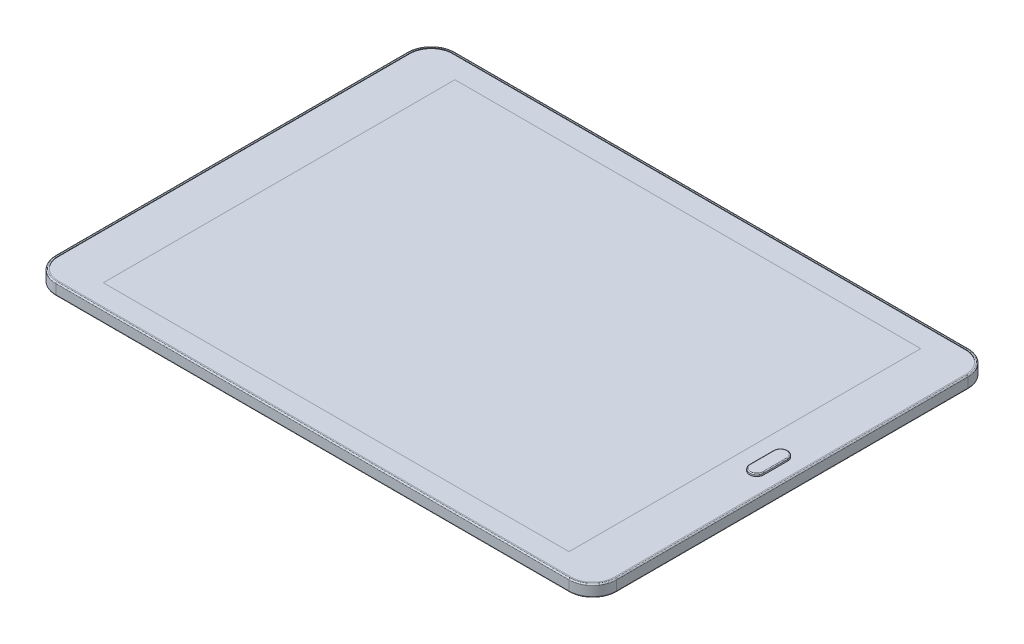
SolidWorks part; units mm, degrees
ref_plane "Front Plane" through (0, 0, 0) normal (0, 0, 1) x (1, 0, 0)
ref_plane "Top Plane" through (0, 0, 0) normal (0, 1, 0) x (1, 0, 0)
ref_plane "Right Plane" through (0, 0, 0) normal (1, 0, 0) x (0, 0, -1)
sketch "Sketch1" plane through (0, 0, 0) normal (0, 1, 0) x (1, 0, 0)
  line L1 (108, 84) -> (-108, 84)
  line L2 (118, 74) -> (118, -74)
  line L3 (108, -84) -> (-108, -84)
  line L4 (-118, 74) -> (-118, -74)
  line L5 (118, 84) -> (-118, -84) construction
  line L6 (118, -84) -> (-118, 84) construction
  arc A0 (-108, -84) -> (-118, -74) centre (-108, -74) cw
  arc A1 (118, -74) -> (108, -84) centre (108, -74) cw
  arc A2 (108, 84) -> (118, 74) centre (108, 74) cw
  arc A3 (-108, 84) -> (-118, 74) centre (-108, 74) ccw
  point P0 (0, 0)
  dimension "D3" = 10
  dimension "D1" = 236
  dimension "D2" = 168
extrude "Boss-Extrude1" add sketch "Sketch1" along normal blind 5
sketch "Sketch2" plane through (0, 5, 0) normal (0, 1, 0) x (1, 0, 0)
  line L8 (-108, -83) -> (108, -83)
  line L9 (117, -74) -> (117, 74)
  line L10 (108, 83) -> (-108, 83)
  line L11 (-117, 74) -> (-117, -74)
  line L12 (-108, -83) -> (108, -83)
  line L13 (117, -74) -> (117, 74)
  line L14 (108, 83) -> (-108, 83)
  line L15 (-117, 74) -> (-117, -74)
  arc A8 (-117, -74) -> (-108, -83) centre (-108, -74) ccw
  arc A9 (108, -83) -> (117, -74) centre (108, -74) ccw
  arc A10 (117, 74) -> (108, 83) centre (108, 74) ccw
  arc A11 (-108, 83) -> (-117, 74) centre (-108, 74) ccw
  arc A12 (-117, -74) -> (-108, -83) centre (-108, -74) ccw
  arc A13 (108, -83) -> (117, -74) centre (108, -74) ccw
  arc A14 (117, 74) -> (108, 83) centre (108, 74) ccw
  arc A15 (-108, 83) -> (-117, 74) centre (-108, 74) ccw
  dimension "D1" = 1
extrude "Cut-Extrude1" cut sketch "Sketch2" against normal blind 0.2
sketch "Sketch3" plane through (0, 4.8, 0) normal (0, 1, 0) x (1, 0, 0)
  line L0 (108, 84) -> (-108, 84) construction
  line L1 (-98, 74) -> (98, 74)
  line L2 (-98, 74) -> (-98, -74)
  line L3 (-98, -74) -> (98, -74)
  line L4 (98, 74) -> (98, -74)
  line L6 (-108, -84) -> (108, -84) construction
  line L7 (118, -74) -> (118, 74) construction
  line L8 (-118, 74) -> (-118, -74) construction
  dimension "D1" = 10
  dimension "D2" = 10
  dimension "D3" = 20
  dimension "D4" = 20
split line "Split Line1"
sketch "Sketch6" plane through (0, 4.8, 0) normal (0, 1, 0) x (1, 0, 0)
  line L0 (0, 0) -> (108, 0) construction
  line L1 (108, 5) -> (108, -5) construction
  line L2 (111, 5) -> (111, -5)
  line L3 (105, 5) -> (105, -5)
  line L4 (118, -74) -> (118, 74) construction
  arc A0 (111, 5) -> (105, 5) centre (108, 5) ccw
  arc A1 (105, -5) -> (111, -5) centre (108, -5) ccw
  point P5 (108, 0)
  dimension "D1" = 10
  dimension "D2" = 6
  dimension "D3" = 10
extrude "Boss-Extrude2" add sketch "Sketch6" along normal blind 1
fillet "Fillet1" radius 0.4 4 edges at (105, 5.8, 0) (108, 5.8, -8) (111, 5.8, 0) (108, 5.8, 8)
sketch "Sketch7" plane through (0, 0, 0) normal (0, -1, 0) x (1, 0, 0)
  line L0 (-109, 0) -> (0, 0) construction
  line L1 (-112, 6) -> (-106, 6)
  line L2 (-115, 3) -> (-115, -3)
  line L3 (-112, -6) -> (-106, -6)
  line L4 (-103, 3) -> (-103, -3)
  line L5 (-115, 6) -> (-103, -6) construction
  line L6 (-115, -6) -> (-103, 6) construction
  line L7 (-118, -74) -> (-118, 74) construction
  arc A0 (-115, -3) -> (-112, -6) centre (-112, -3) ccw
  arc A1 (-106, -6) -> (-103, -3) centre (-106, -3) ccw
  arc A2 (-106, 6) -> (-103, 3) centre (-106, 3) cw
  arc A3 (-112, 6) -> (-115, 3) centre (-112, 3) ccw
  point P0 (-109, 0)
  dimension "D4" = 3
  dimension "D1" = 9
  dimension "D2" = 12
  dimension "D3" = 12
extrude "Boss-Extrude3" add sketch "Sketch7" along normal blind 1
sketch "Sketch8" plane through (0, -1, 0) normal (0, -1, 0) x (1, 0, 0)
  line L8 (-112, -5) -> (-106, -5)
  line L9 (-104, -3) -> (-104, 3)
  line L10 (-106, 5) -> (-112, 5)
  line L11 (-114, 3) -> (-114, -3)
  line L12 (-112, -5) -> (-106, -5)
  line L13 (-104, -3) -> (-104, 3)
  line L14 (-106, 5) -> (-112, 5)
  line L15 (-114, 3) -> (-114, -3)
  arc A8 (-114, -3) -> (-112, -5) centre (-112, -3) ccw
  arc A9 (-106, -5) -> (-104, -3) centre (-106, -3) ccw
  arc A10 (-104, 3) -> (-106, 5) centre (-106, 3) ccw
  arc A11 (-112, 5) -> (-114, 3) centre (-112, 3) ccw
  arc A12 (-114, -3) -> (-112, -5) centre (-112, -3) ccw
  arc A13 (-106, -5) -> (-104, -3) centre (-106, -3) ccw
  arc A14 (-104, 3) -> (-106, 5) centre (-106, 3) ccw
  arc A15 (-112, 5) -> (-114, 3) centre (-112, 3) ccw
  dimension "D1" = 1
extrude "Cut-Extrude2" cut sketch "Sketch8" against normal blind 0.2
fillet "Fillet2" radius 0.8 8 edges at (-114.1213, 0, -5.1213) (-115, 0, 0) (-114.1213, 0, 5.1213) (-109, 0, 6) (-103.8787, 0, 5.1213) (-103, 0, 0) (-103.8787, 0, -5.1213) (-109, 0, -6)
sketch "Sketch9" plane through (0, 0, 0) normal (0, -1, 0) x (1, 0, 0)
  line L0 (0, 0) -> (0, 68) construction
  line L1 (-90.5, 68) -> (90.5, 68) construction
  line L2 (-108, 84) -> (108, 84) construction
  circle A0 centre (-90.5, 68) radius 3
  circle A1 centre (90.5, 68) radius 3
  dimension "D3" = 6
  dimension "D4" = 6
  dimension "D1" = 181
  dimension "D2" = 16
extrude "Cut-Extrude3" cut sketch "Sketch9" against normal blind 0.2
fillet "Fillet3" radius 0.5 8 edges at (-115.0711, 0, 81.0711) (-118, 0, 0) (-115.0711, 0, -81.0711) (0, 0, -84) (115.0711, 0, -81.0711) (118, 0, 0) (115.0711, 0, 81.0711) (0, 0, 84)
sketch "Sketch10" plane through (0, 0, -84) normal (0, 0, -1) x (-1, 0, 0)
  line L0 (108, 2.75) -> (69.5, 2.75) construction
  line L1 (48, 2) -> (91, 2) construction
  line L2 (48, 2.7) -> (48, 2.8)
  line L3 (48, 3.5) -> (91, 3.5) construction
  line L4 (91, 2.7) -> (91, 2.8)
  line L5 (48, 2) -> (91, 3.5) construction
  line L6 (48, 3.5) -> (91, 2) construction
  line L7 (108, 5) -> (108, 0.5) construction
  line L8 (48.7, 3.5) -> (68.3, 3.5)
  line L9 (69, 2.8) -> (69, 2.7)
  line L10 (68.3, 2) -> (48.7, 2)
  line L11 (90.3, 3.5) -> (79.7, 3.5)
  line L12 (79, 2.8) -> (79, 2.7)
  line L13 (79.7, 2) -> (90.3, 2)
  line L14 (118, 5) -> (118, 0.5) construction
  arc A0 (48, 2.8) -> (48.7, 3.5) centre (48.7, 2.8) cw
  arc A1 (48.7, 2) -> (48, 2.7) centre (48.7, 2.7) cw
  arc A2 (69, 2.7) -> (68.3, 2) centre (68.3, 2.7) cw
  arc A3 (68.3, 3.5) -> (69, 2.8) centre (68.3, 2.8) cw
  arc A4 (79.7, 3.5) -> (79, 2.8) centre (79.7, 2.8) ccw
  arc A5 (79, 2.7) -> (79.7, 2) centre (79.7, 2.7) ccw
  arc A6 (90.3, 2) -> (91, 2.7) centre (90.3, 2.7) ccw
  arc A7 (90.3, 3.5) -> (91, 2.8) centre (90.3, 2.8) cw
  point P0 (69.5, 2.75)
  point P23 (69, 2)
  point P26 (69, 3.5)
  point P29 (79, 3.5)
  point P32 (79, 2)
  dimension "D6" = 0.7
  dimension "D1" = 43
  dimension "D2" = 1.5
  dimension "D3" = 10
  dimension "D4" = 12
  dimension "D5" = 27
extrude "Boss-Extrude4" add sketch "Sketch10" along normal blind 1
fillet "Fillet4" radius 0.5 8 edges at (115.0711, 5, 81.0711) (0, 5, 84) (-115.0711, 5, 81.0711) (-118, 5, 0) (-115.0711, 5, -81.0711) (0, 5, -84) (115.0711, 5, -81.0711) (118, 5, 0)
fillet "Fillet5" radius 0.5 8 edges at (-114.1213, -1, 5.1213) (-109, -1, 6) (-103.8787, -1, 5.1213) (-103, -1, 0) (-103.8787, -1, -5.1213) (-109, -1, -6) (-114.1213, -1, -5.1213) (-115, -1, 0)
fillet "Fillet7" radius 0.2 2 edges at (90.5, 0, 65) (-90.5, 0, 65)
